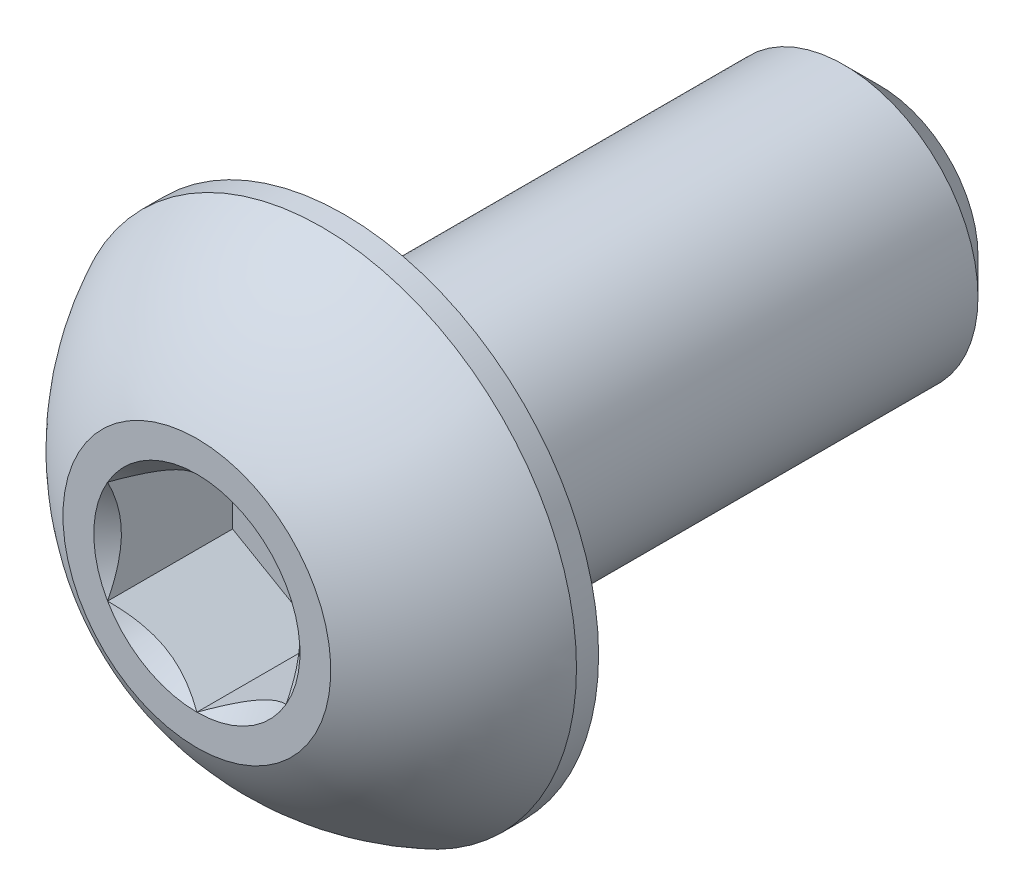
SolidWorks part; units mm, degrees
ref_plane "Front Plane" through (0, 0, 0) normal (0, 0, 1) x (1, 0, 0)
ref_plane "Top Plane" through (0, 0, 0) normal (0, 1, 0) x (1, 0, 0)
ref_plane "Right Plane" through (0, 0, 0) normal (1, 0, 0) x (0, 0, -1)
sketch "Sketch1" plane through (0, 0, 0) normal (1, 0, 0) x (0, 0, -1)
  line L0 (-3.825, 0) -> (3.825, 0) construction
  line L1 (-2.175, 2.85) -> (-2.175, -2.85) construction
  line L2 (3.825, 1.5) -> (3.825, -1.5) construction
  line L3 (3.7937, 1.5541) -> (4.0437, 1.1211) construction
  line L4 (4.0437, 1.1211) -> (4.2937, 1.5541) construction
  line L5 (4.2937, 1.5541) -> (3.7937, 1.5541) construction
  line L6 (3.825, 1.5) -> (4.2625, 1.5) construction
  line L7 (4.0437, 1.5541) -> (4.0437, 1.5) construction
  line L8 (4.0437, 1.5) -> (4.0437, 1.1752) construction
  line L9 (4.0437, 1.1752) -> (4.0437, 1.1211) construction
  line L10 (4.0125, 1.1752) -> (4.075, 1.1752)
  line L11 (3.8094, 1.5271) -> (4.2781, 1.5271)
  line L12 (4.075, 1.1752) -> (4.2781, 1.5271)
  line L13 (4.0125, 1.1752) -> (3.8094, 1.5271)
  line L14 (-3.825, 1) -> (-3.825, -1) construction
  line L15 (3.825, 1.5) -> (-2.175, 1.5) construction
  point P3 (-2.175, 0)
  point P6 (-2.425, 0)
  point P21 (4.0437, 1.5271)
  point P24 (-2.4225, 2.85)
  point P25 (2.575, -1.5)
  point P26 (-3.825, 1.5)
  dimension "Head Height" = 1.65
  dimension "Length" = 6
  dimension "Head Dia" = 5.7
  dimension "Thread Dia" = 3
  dimension "Pitch" = 0.5
  dimension "D2" = 0.0625
  dimension "Drive Size" = 2
  dimension "D1" = 1.4
  dimension "D3" = 0.2475
  dimension "D4" = 1.25
sketch "Sketch2" plane through (0, 0, 0) normal (1, 0, 0) x (0, 0, -1)
  line L0 (-3.825, 0) -> (3.825, 0)
  line L1 (3.825, 0) -> (3.825, 1.1)
  line L2 (3.825, 1.5) -> (3.825, -1.5) construction
  line L3 (3.825, 1.1) -> (3.425, 1.5)
  line L4 (3.425, 1.5) -> (-2.175, 1.5)
  line L5 (-2.175, 2.85) -> (-2.175, -2.85) construction
  line L6 (-2.175, 1.5) -> (-2.175, 2.85)
  line L7 (-2.175, 2.85) -> (-2.4225, 2.85)
  line L8 (3.825, 1.5) -> (4.2625, 1.5) construction
  line L9 (-3.825, 0) -> (-3.825, 1.5)
  arc A0 (-3.825, 1.5) -> (-2.4225, 2.85) centre (-1.0302, 0) cw
  dimension "D1" = 0.4
  dimension "D2" = 45
revolve "Revolve1" add sketch "Sketch2" angle 360 about L0
sketch "Sketch3" plane through (0, 0, 3.825) normal (0, 0, 1) x (1, 0, 0)
  line L1 (0, 1.1547) -> (-1, 0.5774)
  line L2 (-1, 0.5774) -> (-1, -0.5774)
  line L3 (-1, -0.5774) -> (0, -1.1547)
  line L4 (0, -1.1547) -> (1, -0.5774)
  line L5 (1, -0.5774) -> (1, 0.5774)
  line L6 (1, 0.5774) -> (0, 1.1547)
  circle A0 centre (0, 0) radius 1 construction
  dimension "D1" = 2
extrude "Cut-Extrude1" cut sketch "Sketch3" against normal up to vertex (1.4 mm away) up to point (0, 0, 2.425)
sketch "Sketch4" plane through (0, 0, 3.825) normal (0, 0, 1) x (1, 0, 0)
  circle A0 centre (0, 0) radius 1.1547
extrude "Cut-Extrude2" cut sketch "Sketch4" against normal blind 10 draft 45
split "Split1" [suppressed] bodies to split 106
sketch "Sketch5" [suppressed] plane through (0, 0, -3.825) normal (0, 0, -1) x (-1, 0, 0)
  circle A0 centre (0, 0) radius 1.5 construction
  circle A1 centre (0, 0) radius 1.5
curve "Helix/Spiral1" [suppressed] pitch 0.5 height 6.5 turns 13
sketch "Sketch6" [suppressed] plane through (0, 0, 0) normal (1, 0, 0) x (0, 0, -1)
  line L0 (4.0125, 1.1752) -> (4.075, 1.1752) construction
  line L1 (4.0125, 1.1752) -> (3.8094, 1.5271) construction
  line L2 (3.8094, 1.5271) -> (4.2781, 1.5271) construction
  line L3 (4.075, 1.1752) -> (4.2781, 1.5271) construction
  line L4 (4.0125, 1.1752) -> (4.075, 1.1752)
  line L5 (4.0125, 1.1752) -> (3.8094, 1.5271)
  line L6 (3.8094, 1.5271) -> (4.2781, 1.5271)
  line L7 (4.075, 1.1752) -> (4.2781, 1.5271)
sweep "Cut-Sweep1" [suppressed] cut profiles "Sketch6" path "Helix/Spiral1"
sketch "Sketch7" [suppressed] plane through (0, 0, 2.175) normal (0, 0, -1) x (-1, 0, 0)
  circle A1 centre (0, 0) radius 1.5
  circle A2 centre (0, 0) radius 1.5
  dimension "D1" = 0
extrude "Boss-Extrude1" [suppressed] add sketch "Sketch7" along normal blind 10 draft 30
equation "\"D2@Sketch1\" = \"Pitch@Sketch1\" / 8"
equation "\"D1@Sketch1\"=\"Drive Size@Sketch1\"*.7"
equation "\"D3@Sketch1\"=\"Head Height@Sketch1\"*.15"
equation "\"D1@Sketch2\"=\"Pitch@Sketch1\"*.8"
equation "\"D1@Sketch3\"=\"Drive Size@Sketch1\""
equation "\"D4@Helix/Spiral1\"=\"Pitch@Sketch1\""
equation "\"D3@Helix/Spiral1\"=\"Length@Sketch1\"+\"Pitch@Sketch1\""
equation "\"D4@Sketch1\"=\"Pitch@Sketch1\"*2.5"
